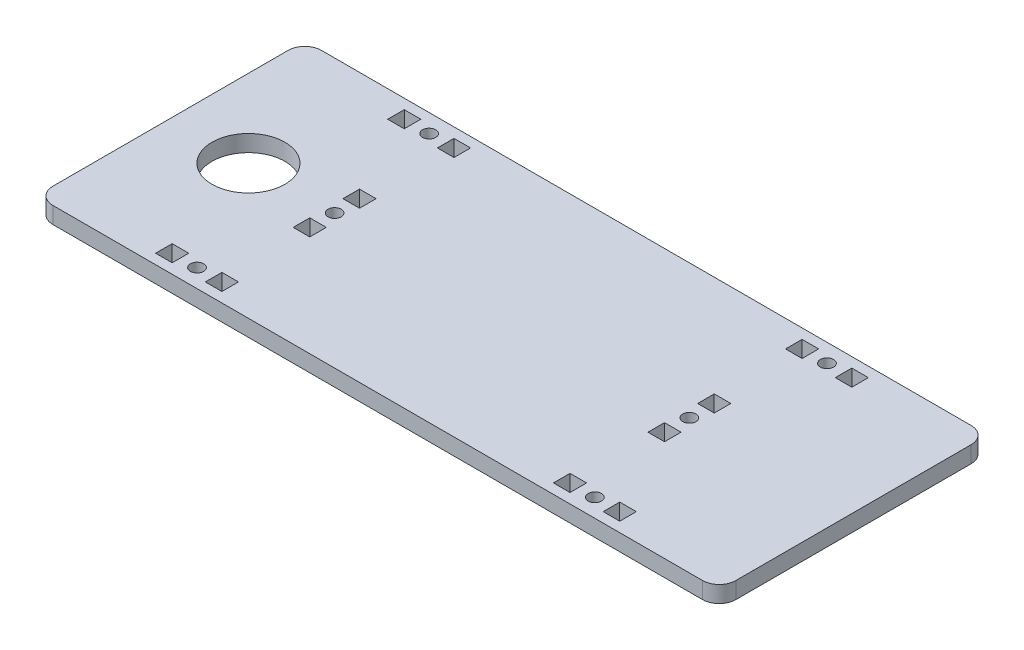
SolidWorks part; units mm, degrees
ref_plane "Front Plane" through (0, 0, 0) normal (0, 0, 1) x (1, 0, 0)
ref_plane "Top Plane" through (0, 0, 0) normal (0, 1, 0) x (1, 0, 0)
ref_plane "Right Plane" through (0, 0, 0) normal (1, 0, 0) x (0, 0, -1)
sketch "Sketch1" plane through (0, 0, 0) normal (0, 1, 0) x (1, 0, 0)
  line L0 (5.1027, 53.6563) -> (5.1027, -27.3437) construction
  line L1 (-97.8973, 53.6563) -> (108.1027, 53.6563)
  line L2 (-97.8973, 53.6563) -> (-97.8973, -27.3437)
  line L3 (-97.8973, -27.3437) -> (108.1027, -27.3437)
  line L4 (108.1027, 53.6563) -> (108.1027, -27.3437)
  line L5 (-97.8973, 13.1563) -> (108.1027, 13.1563) construction
  line L6 (60.1027, 45.6563) -> (55.1027, 45.6563)
  line L7 (-64.8973, 50.6563) -> (-59.8973, 50.6563)
  line L8 (-64.8973, 50.6563) -> (-64.8973, 45.6563)
  line L9 (-64.8973, 45.6563) -> (-59.8973, 45.6563)
  line L10 (-59.8973, 50.6563) -> (-59.8973, 45.6563)
  line L11 (-49.8973, 50.6563) -> (-44.8973, 50.6563)
  line L12 (-49.8973, 50.6563) -> (-49.8973, 45.6563)
  line L13 (-49.8973, 45.6563) -> (-44.8973, 45.6563)
  line L14 (-44.8973, 50.6563) -> (-44.8973, 45.6563)
  line L15 (55.1027, 50.6563) -> (55.1027, 45.6563)
  line L16 (60.1027, 50.6563) -> (55.1027, 50.6563)
  line L17 (60.1027, 50.6563) -> (60.1027, 45.6563)
  line L18 (70.1027, 50.6563) -> (70.1027, 45.6563)
  line L19 (75.1027, 50.6563) -> (70.1027, 50.6563)
  line L20 (75.1027, 50.6563) -> (75.1027, 45.6563)
  line L21 (75.1027, 45.6563) -> (70.1027, 45.6563)
  line L22 (75.1027, -24.3437) -> (75.1027, -19.3437)
  line L23 (75.1027, -19.3437) -> (70.1027, -19.3437)
  line L24 (75.1027, -24.3437) -> (70.1027, -24.3437)
  line L25 (70.1027, -24.3437) -> (70.1027, -19.3437)
  line L26 (60.1027, -24.3437) -> (60.1027, -19.3437)
  line L27 (60.1027, -19.3437) -> (55.1027, -19.3437)
  line L28 (55.1027, -24.3437) -> (55.1027, -19.3437)
  line L29 (60.1027, -24.3437) -> (55.1027, -24.3437)
  line L30 (-49.8973, -24.3437) -> (-44.8973, -24.3437)
  line L31 (-44.8973, -24.3437) -> (-44.8973, -19.3437)
  line L32 (-49.8973, -19.3437) -> (-44.8973, -19.3437)
  line L33 (-49.8973, -24.3437) -> (-49.8973, -19.3437)
  line L34 (-64.8973, -24.3437) -> (-59.8973, -24.3437)
  line L35 (-64.8973, -24.3437) -> (-64.8973, -19.3437)
  line L36 (-64.8973, -19.3437) -> (-59.8973, -19.3437)
  line L37 (-59.8973, -24.3437) -> (-59.8973, -19.3437)
  line L42 (-45.8973, 18.1563) -> (-45.8973, 23.1563)
  line L43 (-50.8973, 8.1563) -> (-45.8973, 8.1563)
  line L44 (-50.8973, 8.1563) -> (-50.8973, 3.1563)
  line L45 (-50.8973, 3.1563) -> (-45.8973, 3.1563)
  line L46 (-45.8973, 8.1563) -> (-45.8973, 3.1563)
  line L47 (-50.8973, 23.1563) -> (-45.8973, 23.1563)
  line L48 (-50.8973, 18.1563) -> (-50.8973, 23.1563)
  line L49 (-50.8973, 18.1563) -> (-45.8973, 18.1563)
  line L50 (56.1027, 8.1563) -> (56.1027, 3.1563)
  line L51 (61.1027, 3.1563) -> (56.1027, 3.1563)
  line L52 (61.1027, 8.1563) -> (61.1027, 3.1563)
  line L53 (61.1027, 8.1563) -> (56.1027, 8.1563)
  line L54 (56.1027, 18.1563) -> (56.1027, 23.1563)
  line L55 (61.1027, 18.1563) -> (56.1027, 18.1563)
  line L56 (61.1027, 18.1563) -> (61.1027, 23.1563)
  line L57 (61.1027, 23.1563) -> (56.1027, 23.1563)
  circle A0 centre (-54.8973, 48.1563) radius 2
  circle A1 centre (-54.8973, -21.8437) radius 2
  circle A2 centre (65.1027, -21.8437) radius 2
  circle A3 centre (65.1027, 48.1563) radius 2
  circle A5 centre (-48.3973, 13.1563) radius 2
  circle A6 centre (58.6027, 13.1563) radius 2
  circle A7 centre (-74.3973, 13.1563) radius 11
  point P36 (-59.8973, -19.3437)
  point P55 (-45.8973, 5.6563)
  dimension "D7" = 4
  dimension "D8" = 4
  dimension "D12" = 22
  dimension "D1" = 206
  dimension "D2" = 81
  dimension "D3" = 5
  dimension "D4" = 10
  dimension "D5" = 3
  dimension "D6" = 50
  dimension "D9" = 51
  dimension "D10" = 5
  dimension "D11" = 5.5
extrude "Boss-Extrude4" add sketch "Sketch1" along normal blind 5
fillet "Fillet9" radius 5 4 edges at (108.1027, 2.5, -53.6563) (108.1027, 2.5, 27.3437) (-97.8973, 2.5, -53.6563) (-97.8973, 2.5, 27.3437)
